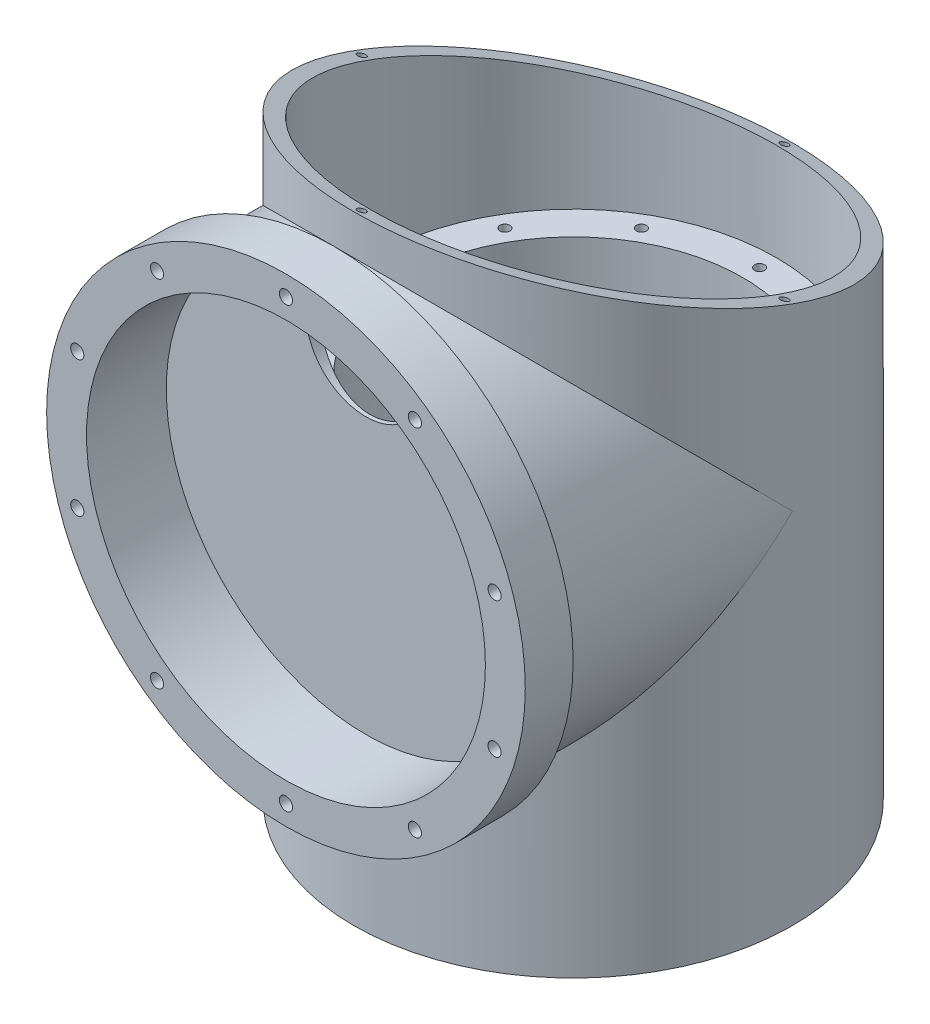
SolidWorks part; units mm, degrees
ref_plane "前视基准面" through (0, 0, 0) normal (0, 0, 1) x (1, 0, 0)
ref_plane "上视基准面" through (0, 0, 0) normal (0, 1, 0) x (1, 0, 0)
ref_plane "右视基准面" through (0, 0, 0) normal (1, 0, 0) x (0, 0, -1)
sketch "草图1" plane through (0, 0, 0) normal (0, 0, 1) x (1, 0, 0)
  circle A0 centre (0, 0) radius 55
  dimension "D1" = 110
extrude "凸台-拉伸4" add sketch "草图1" along normal blind 60
sketch "草图7" plane through (0, 0, 0) normal (0, 1, 0) x (1, 0, 0)
  circle A0 centre (0, 0) radius 55
  dimension "D1" = 110
extrude "凸台-拉伸5" add sketch "草图7" along normal blind 65 and the other way blind 90
sketch "草图8" plane through (0, 65, 0) normal (0, 1, 0) x (1, 0, 0)
  circle A0 centre (0, 0) radius 35
  dimension "D1" = 70
extrude "切除-拉伸1" cut sketch "草图8" against normal through all
sketch "草图10" plane through (0, 0, 60) normal (0, 0, 1) x (1, 0, 0)
  circle A0 centre (0, 0) radius 60
  dimension "D1" = 120
extrude "凸台-拉伸6" add sketch "草图10" along normal blind 12
sketch "草图11" plane through (0, 0, 72) normal (0, 0, 1) x (1, 0, 0)
  circle A0 centre (0, 0) radius 35
  dimension "D1" = 70
extrude "切除-拉伸3" cut sketch "草图11" against normal blind 20
hole_wizard "M4 螺纹孔1" positions "草图13" profile "草图12" tap size "M4" standard "GB"
sketch "草图13" plane through (0, 0, 72) normal (0, 0, 1) x (1, 0, 0)
  line L0 (0, 0) -> (0, 69.8149) construction
  circle A0 centre (0, 0) radius 55 construction
  point P0 (0, 55)
  dimension "D1" = 110
sketch "草图12" plane through (0, 55, 72) normal (1, 0, 0) x (0, -1, 0)
  line L0 (0, 0) -> (0, 11.0914)
  line L1 (0, 11.0914) -> (1.65, 10.1)
  line L2 (1.65, 10.1) -> (1.65, 0)
  line L5 (1.65, 0) -> (0, 0)
  line L10 (0, 11.0914) -> (-1.65, 10.1) construction
  line L11 (0, -6.35) -> (0, 107.95) construction
  dimension "螺纹孔钻头直径" = 3.3
  dimension "螺纹孔钻头深度" = 10.1
  dimension "导头角度" = 118
cosmetic thread "孔螺蚊线1" parameters "D1"=8, "D2"=4
ref_axis "基准轴1" through (0, 0, 49.9565) along (0, 0, 1)
pattern_circular "阵列(圆周)1" count 10 over 360 about axis through (0, 0, 49.9565) along (0, 0, 1) of "M4 螺纹孔1"
sketch "草图14" plane through (0, 0, 72) normal (0, 0, 1) x (1, 0, 0)
  circle A0 centre (0, 0) radius 50
  dimension "D1" = 100
extrude "切除-拉伸4" cut sketch "草图14" against normal blind 20
sketch "草图16" plane through (0, -90, 0) normal (0, -1, 0) x (1, 0, 0)
  circle A0 centre (0, 0) radius 47.5
  dimension "D1" = 95
extrude "切除-拉伸5" cut sketch "草图16" against normal blind 25
hole_wizard "M3 螺纹孔1" positions "草图18" profile "草图17" tap size "M3" standard "GB"
sketch "草图18" plane through (0, -65, 0) normal (0, -1, 0) x (-1, 0, 0)
  line L0 (0, 0) -> (0, -86.2725) construction
  line L1 (0, -49.9565) -> (0, -119.9565) construction
  circle A0 centre (0, 0) radius 42 construction
  point P0 (0, -42)
  dimension "D1" = 84
sketch "草图17" plane through (0, -65, 42) normal (1, 0, 0) x (0, 0, -1)
  line L0 (0, 0) -> (0, 8.2511)
  line L1 (0, 8.2511) -> (1.25, 7.5)
  line L2 (1.25, 7.5) -> (1.25, 0)
  line L5 (1.25, 0) -> (0, 0)
  line L10 (0, 8.2511) -> (-1.25, 7.5) construction
  line L11 (0, -6.35) -> (0, 107.95) construction
  dimension "螺纹孔钻头直径" = 2.5
  dimension "螺纹孔钻头深度" = 7.5
  dimension "导头角度" = 118
cosmetic thread "孔螺蚊线2" parameters "D1"=6, "D2"=3
ref_axis "基准轴2" through (0, -90, 0) along (0, 1, 0)
pattern_circular "阵列(圆周)2" count 12 over 360 about axis through (0, -90, 0) along (0, 1, 0) of "M3 螺纹孔1"
sketch "草图19" plane through (0, 65, 0) normal (0, 1, 0) x (1, 0, 0)
  circle A0 centre (0, 0) radius 51
  dimension "D1" = 102
extrude "切除-拉伸6" cut sketch "草图19" against normal offset from surface (63 mm away) 67 contours A0 up to face at (-21, -65, 35.1231)
sketch "草图21" plane through (0, 2, 0) normal (0, 1, 0) x (1, 0, 0)
  circle A0 centre (0, 0) radius 42.49
  dimension "D1" = 84.98
extrude "切除-拉伸7" cut sketch "草图21" against normal offset from surface (57 mm away) 10 up to face at (-21, -65, 35.1231)
hole_wizard "M3 螺纹孔2" positions "草图23" profile "草图22" tap size "M3" standard "GB"
sketch "草图23" plane through (0, 2, 0) normal (0, 1, 0) x (1, 0, 0)
  line L0 (0, 0) -> (0, 59.3621) construction
  circle A0 centre (0, 0) radius 46.75 construction
  point P0 (0, 46.75)
  dimension "D1" = 93.5
sketch "草图22" plane through (0, 2, -46.75) normal (1, 0, 0) x (0, 0, 1)
  line L0 (0, 0) -> (0, 8.2511)
  line L1 (0, 8.2511) -> (1.25, 7.5)
  line L2 (1.25, 7.5) -> (1.25, 0)
  line L5 (1.25, 0) -> (0, 0)
  line L10 (0, 8.2511) -> (-1.25, 7.5) construction
  line L11 (0, -6.35) -> (0, 107.95) construction
  dimension "螺纹孔钻头直径" = 2.5
  dimension "螺纹孔钻头深度" = 7.5
  dimension "导头角度" = 118
cosmetic thread "孔螺蚊线3" parameters "D1"=6, "D2"=3
pattern_circular "阵列(圆周)3" count 12 over 360 about axis through (0, -90, 0) along (0, 1, 0) of "M3 螺纹孔2"
sketch "草图24" plane through (0, 0, 0) normal (1, 0, 0) x (0, 0, -1)
  line L0 (-55, 65) -> (55, 65)
  line L1 (55, 65) -> (55, 24.9633)
  line L2 (55, -90) -> (55, 65) construction
  line L3 (55, 24.9633) -> (-55, 65)
  dimension "D1" = 20
extrude "切除-拉伸8" cut sketch "草图24" against normal through all and the other way through all
ref_plane "基准面1" through (0, 65, 0) normal (0, 1, 0) x (1, 0, 0)
sketch "草图25" plane through (0, 65, 0) normal (0, 1, 0) x (1, 0, 0)
  line L0 (-46.2503, 0) -> (61.4615, 0) construction
  circle A0 centre (0, 0) radius 53 construction
  circle A1 centre (53, 0) radius 1
  circle A2 centre (-53, 0) radius 1
  dimension "D1" = 106
  dimension "D2" = 2
  dimension "D3" = 2
extrude "切除-拉伸9" cut sketch "草图25" against normal blind 26 contours A2 | A1
sketch "草图26" plane through (0, 65, 0) normal (0, 1, 0) x (1, 0, 0)
  line L0 (0, 0) -> (0, 59.2682) construction
  circle A0 centre (0, 0) radius 53 construction
  circle A1 centre (0, 53) radius 1
  dimension "D1" = 106
  dimension "D2" = 2
extrude "切除-拉伸10" cut sketch "草图26" against normal blind 46
sketch "草图27" plane through (0, 65, 0) normal (0, 1, 0) x (1, 0, 0)
  line L0 (0, 0) -> (0, -81.7723) construction
  circle A0 centre (0, 0) radius 53 construction
  circle A1 centre (0, -53) radius 1
  dimension "D1" = 106
  dimension "D2" = 2
extrude "切除-拉伸11" cut sketch "草图27" against normal blind 7
sketch "草图28" plane through (0, 0, 52) normal (0, 0, 1) x (1, 0, 0)
  line L0 (-36.6606, 34) -> (36.6606, 34) construction
  line L1 (0, 0) -> (0, 69.0515) construction
  line L2 (0, -90) -> (0, 65) construction
  circle A0 centre (0, 0) radius 50 construction
  circle A1 centre (0, 34) radius 15
  dimension "D2" = 30
  dimension "D1" = 34
extrude "切除-拉伸13" cut sketch "草图28" against normal blind 20 contours A1
